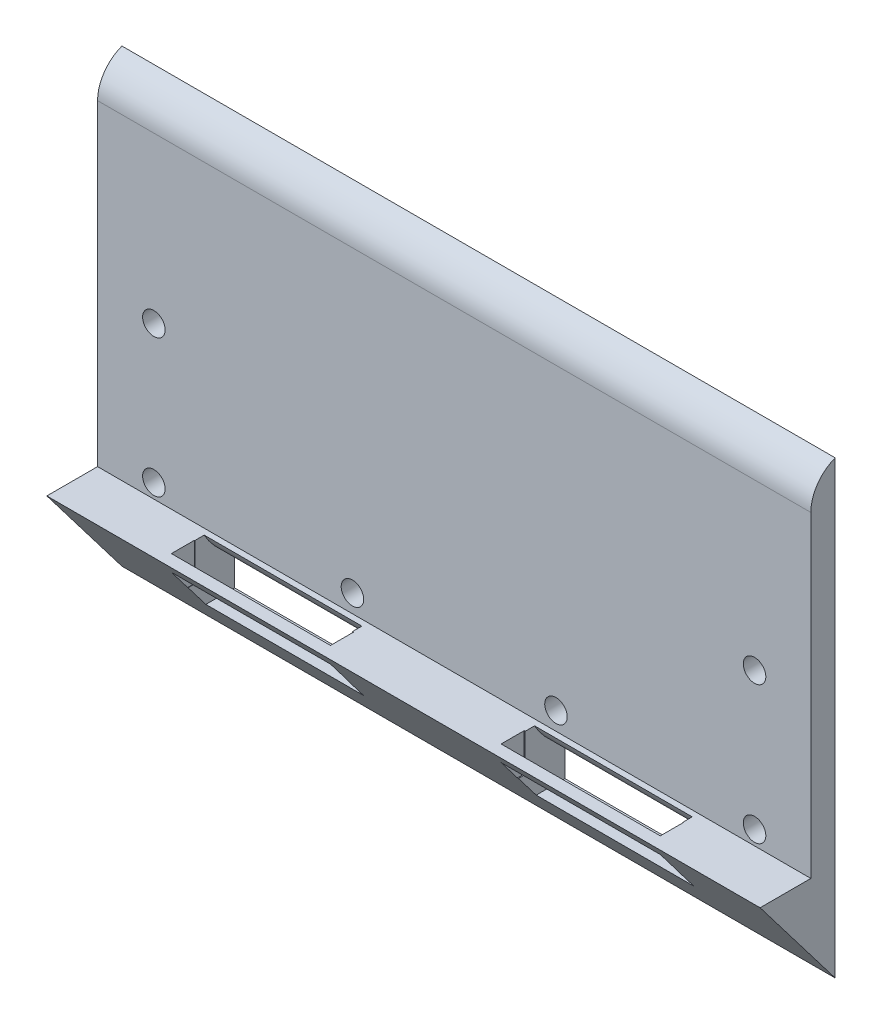
SolidWorks part; units mm, degrees
ref_plane "Alzado" through (0, 0, 0) normal (0, 0, 1) x (1, 0, 0)
ref_plane "Planta" through (0, 0, 0) normal (0, 1, 0) x (1, 0, 0)
ref_plane "Vista lateral" through (0, 0, 0) normal (1, 0, 0) x (0, 0, -1)
sketch "Croquis1" plane through (0, 0, 0) normal (0, 0, 1) x (1, 0, 0)
  line L1 (-47.3043, 32.1205) -> (47.6957, 32.1205)
  line L2 (-47.3043, 32.1205) -> (-47.3043, -17.8795)
  line L3 (-47.3043, -17.8795) -> (47.6957, -17.8795)
  line L4 (47.6957, 32.1205) -> (47.6957, -17.8795)
  dimension "D1" = 50
  dimension "D2" = 95
extrude "Saliente-Extruir1" add sketch "Croquis1" along normal blind 10
sketch "Croquis2" plane through (0, 0, 10) normal (0, 0, 1) x (1, 0, 0)
  line L1 (-32.3043, -8.7558) -> (-11.3043, -8.7558)
  line L2 (-32.3043, -8.7558) -> (-32.3043, -12.8795)
  line L3 (-32.3043, -12.8795) -> (-11.3043, -12.8795)
  line L4 (-11.3043, -8.7558) -> (-11.3043, -12.8795)
  line L5 (-47.3043, 32.1205) -> (-47.3043, -17.8795) construction
  line L6 (11.6957, -12.8795) -> (32.6957, -12.8795)
  line L7 (11.6957, -12.8795) -> (11.6957, -8.7558)
  line L8 (11.6957, -8.7558) -> (32.6957, -8.7558)
  line L9 (32.6957, -12.8795) -> (32.6957, -8.7558)
  line L10 (47.6957, -17.8795) -> (47.6957, 32.1205) construction
  line L11 (-47.3043, -17.8795) -> (47.6957, -17.8795) construction
  dimension "D1" = 4.1237
  dimension "D2" = 21
  dimension "D3" = 4.1237
  dimension "D4" = 21
  dimension "D5" = 15
  dimension "D6" = 15
  dimension "D7" = 5
  dimension "D8" = 5
extrude "Cortar-Extruir1" cut sketch "Croquis2" against normal blind 20
sketch "Croquis3" plane through (-47.3043, 0, 0) normal (-1, 0, 0) x (0, 0, 1)
  line L0 (0, -17.8795) -> (10, -4.7747)
  line L1 (10, 32.1205) -> (10, -17.8795) construction
  line L2 (10, -4.7747) -> (10, -17.8795)
  line L3 (10, -17.8795) -> (0, -17.8795) construction
  line L4 (10, -17.8795) -> (0, -17.8795)
extrude "Cortar-Extruir2" cut sketch "Croquis3" against normal blind 1000
fillet "Redondeo1" radius 5 1 edges at (0.1957, 32.1205, 10)
sketch "Croquis5" plane through (0, 0, 10) normal (0, 0, 1) x (1, 0, 0)
  line L0 (-39.8043, 32.1205) -> (-39.8043, 15.4805) construction
  line L1 (-47.3043, 32.1205) -> (47.6957, 32.1205) construction
  line L2 (-47.3043, 27.1205) -> (-47.3043, -4.7747) construction
  line L3 (0.1957, 27.1205) -> (0.1957, -4.7747) construction
  line L4 (47.6957, 27.1205) -> (-47.3043, 27.1205) construction
  line L5 (47.6957, -4.7747) -> (-47.3043, -4.7747) construction
  line L6 (-47.3043, -17.8795) -> (47.6957, -17.8795) construction
  circle A0 centre (-39.8043, 15.4805) radius 1.5
  circle A3 centre (40.1957, 15.4805) radius 1.5
  circle A4 centre (-13.3578, -2.3795) radius 1.5
  circle A5 centre (13.7493, -2.3795) radius 1.5
  circle A6 centre (-39.8043, -2.8595) radius 1.5
  circle A7 centre (40.1957, -2.8595) radius 1.5
  point P9 (-38.8714, 15.4352)
  point P16 (-39.9822, 15.4805)
  point P27 (-39.2547, 15.4805)
  point P28 (0, 0)
  dimension "D2" = 3
  dimension "D4" = 15.02
  dimension "D5" = 7.5
  dimension "D6" = 3
  dimension "D7" = 3
  dimension "D1" = 18.34
extrude "Cortar-Extruir3" cut sketch "Croquis5" against normal blind 10
sketch "Croquis7" plane through (-47.3043, 0, 0) normal (-1, 0, 0) x (0, 0, 1)
  line L0 (10, -4.7747) -> (4.7908, -4.7747)
  line L2 (5, 32.1205) -> (10, 32.1205)
  line L3 (10, 32.1205) -> (10, -4.7747)
  line L4 (5, 32.1205) -> (3.2408, 32.1205)
  line L5 (5, 32.1205) -> (0, 32.1205) construction
  line L6 (3.2408, 32.1205) -> (3.2408, -4.2927)
  line L7 (4.7908, -4.7747) -> (3.2408, -4.7747)
  line L8 (3.2408, -4.2927) -> (3.2408, -4.7747)
extrude "Cortar-Extruir4" cut sketch "Croquis7" against normal blind 140
sketch "Croquis8" plane through (0, -4.7747, 0) normal (0, 1, 0) x (1, 0, 0)
  line L1 (-32.3592, -5.2853) -> (-11.1678, -5.2853)
  line L2 (-32.3592, -5.2853) -> (-32.3592, -8.3565)
  line L3 (-32.3592, -8.3565) -> (-11.1678, -8.3565)
  line L4 (-11.1678, -5.2853) -> (-11.1678, -8.3565)
  line L5 (11.5592, -5.2853) -> (32.7592, -5.2853)
  line L6 (11.5592, -5.2853) -> (11.5592, -8.3565)
  line L7 (11.5592, -8.3565) -> (32.7592, -8.3565)
  line L8 (32.7592, -5.2853) -> (32.7592, -8.3565)
  dimension "D1" = 3.0712
  dimension "D2" = 21.1914
  dimension "D3" = 3.0712
  dimension "D4" = 21.2
extrude "Cortar-Extruir5" cut sketch "Croquis8" against normal blind 5
fillet "Redondeo2" radius 10 1 edges at (-21.8043, -8.7558, 5.2853)
fillet "Redondeo3" radius 10 1 edges at (22.1957, -8.7558, 5.2853)
sketch "Croquis9" plane through (0, 32.1205, 0) normal (0, 1, 0) x (1, 0, 0)
  line L1 (-47.3043, 0) -> (47.6957, 0)
  line L2 (-47.3043, 0) -> (-47.3043, -3.2408)
  line L3 (-47.3043, -3.2408) -> (47.6957, -3.2408)
  line L4 (47.6957, 0) -> (47.6957, -3.2408)
  line L5 (47.6957, -3.2408) -> (-47.3043, -3.2408) construction
  dimension "D1" = 3.2408
  dimension "D2" = 95
extrude "Saliente-Extruir2" add sketch "Croquis9" along normal blind 10
fillet "Redondeo4" radius 5 1 edges at (0.1957, 42.1205, 3.2408)
